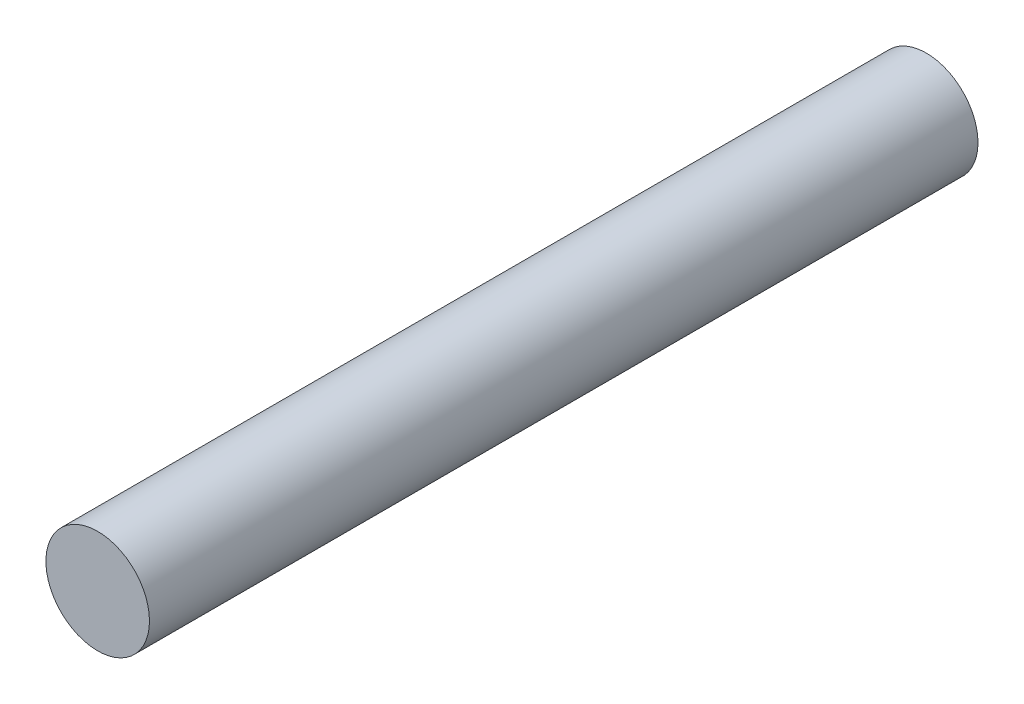
SolidWorks part; units mm, degrees
material "Temperguss"
ref_plane "Ebene vorne" through (0, 0, 0) normal (0, 0, 1) x (1, 0, 0)
ref_plane "Ebene oben" through (0, 0, 0) normal (0, 1, 0) x (1, 0, 0)
ref_plane "Ebene rechts" through (0, 0, 0) normal (1, 0, 0) x (0, 0, -1)
sketch "Skizze1" plane through (0, 0, 0) normal (0, 0, 1) x (1, 0, 0)
  circle A0 centre (-4.1799, 1.2472) radius 1.25
  dimension "D1" = 2.5
extrude "Aufsatz-Linear austragen1" add sketch "Skizze1" along normal blind 20
